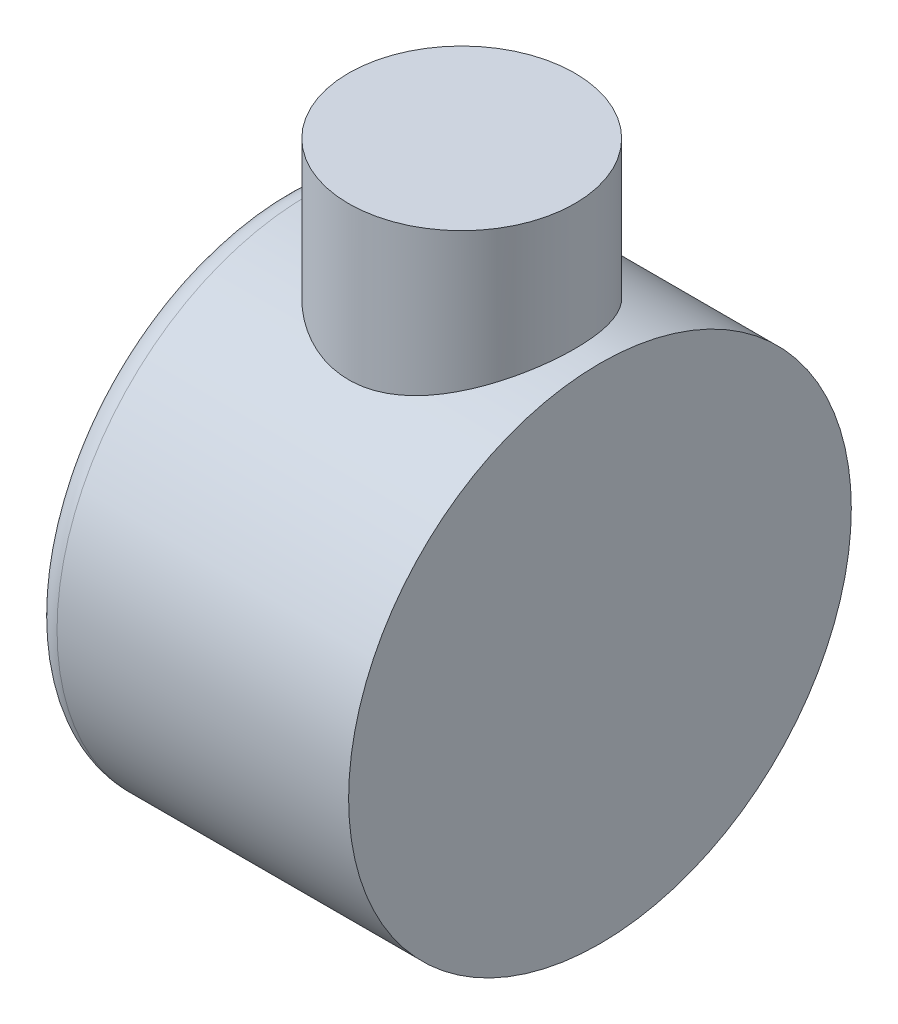
SolidWorks part; units mm, degrees
material "Cast Stainless Steel"
ref_plane "Front Plane" through (0, 0, 0) normal (0, 0, 1) x (1, 0, 0)
ref_plane "Top Plane" through (0, 0, 0) normal (0, 1, 0) x (1, 0, 0)
ref_plane "Right Plane" through (0, 0, 0) normal (1, 0, 0) x (0, 0, -1)
other "Center of Mass"
sketch "Sketch2" plane through (0, 0, 0) normal (1, 0, 0) x (0, 0, -1)
  circle A0 centre (0, 0) radius 50
  dimension "D1" = 100
extrude "Boss-Extrude1" add sketch "Sketch2" along normal blind 55
ref_plane "Plane1" through (27.5, 0, 0) normal (-1, 0, 0) x (0, 0, 1)
sketch "Sketch3" plane through (27.5, 0, 0) normal (-1, 0, 0) x (0, 0, 1)
  line L0 (0, 50) -> (0, 75)
  line L1 (0, 75) -> (22.5, 75)
  line L2 (0, 75) -> (-22.5, 75)
  line L3 (-22.5, 75) -> (-22.5, 44.6514)
  line L4 (22.5, 75) -> (22.5, 44.6514)
  circle A1 centre (0, 0) radius 50
  circle A2 centre (0, 0) radius 50
  dimension "D2" = 25
  dimension "D3" = 22.5
  dimension "D4" = 22.5
  dimension "D1" = 0
revolve "Revolve1" add sketch "Sketch3" angle 360 about L0 region at (27.5, 61.5818, 11.6206)
sketch "Sketch4" plane through (0, 0, 0) normal (-1, 0, 0) x (0, 0, 1)
  circle A1 centre (0, 0) radius 50
  circle A2 centre (0, 0) radius 50
  dimension "D1" = 0
extrude "Boss-Extrude2" add sketch "Sketch4" along normal blind 8
fillet "Fillet1" radius 5 1 edges at (-8, 0, 50)
ref_axis "Axis1" through (55, 0, 0) along (-1, 0, 0)
ref_axis "Axis2" through (27.5, 75, 0) along (0, -1, 0)
ref_point "Point1"
